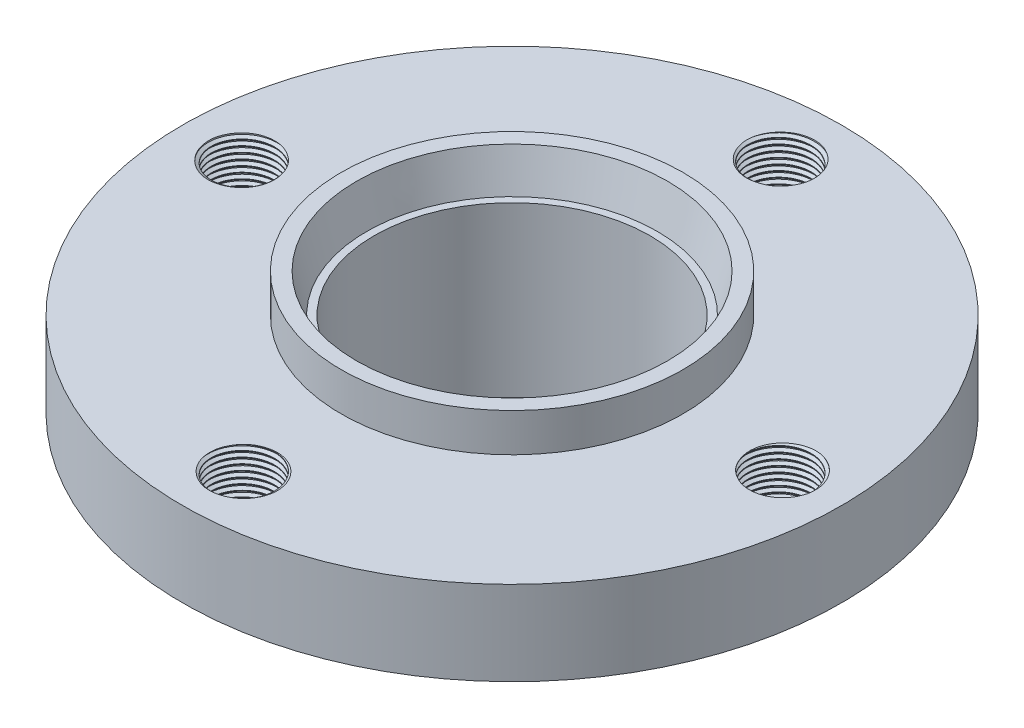
SolidWorks part; units mm, degrees
material "Chrome Stainless Steel"
ref_plane "Front Plane" through (0, 0, 0) normal (0, 0, 1) x (1, 0, 0)
ref_plane "Top Plane" through (0, 0, 0) normal (0, 1, 0) x (1, 0, 0)
ref_plane "Right Plane" through (0, 0, 0) normal (1, 0, 0) x (0, 0, -1)
sketch "Sketch1" plane through (0, 0, 0) normal (0, 0, 1) x (1, 0, 0)
  line L0 (539.3648, 0) -> (36, 0) construction
  line L1 (0, 0) -> (0, 26118.2396) construction
  line L2 (36, 0) -> (44.5, 0)
  line L3 (44.5, 0) -> (44.5, 22)
  line L4 (44.5, 22) -> (86, 22)
  line L5 (86, 22) -> (86, 44)
  line L6 (86, 44) -> (44.5984, 44)
  line L7 (44.5984, 44) -> (44.5984, 54)
  line L8 (44.5984, 54) -> (40.5984, 54)
  line L9 (40.5984, 54) -> (37.919, 44)
  line L10 (37.919, 44) -> (36, 44)
  line L11 (36, 44) -> (36, 0)
  line L12 (0, 0) -> (-26118.2396, 0) construction
  dimension "D1" = 8.5
  dimension "D2" = 22
  dimension "D3" = 41.5
  dimension "D4" = 10
  dimension "D5" = 54
  dimension "D6" = 4
  dimension "D7" = 10
  dimension "D8" = 105
  dimension "D9" = 36
  dimension "D10" = 41.4016
revolve "Revolve3" add sketch "Sketch1" angle 360 about L1
hole_wizard "Ø1.0mm Dowel Hole1" positions "Sketch3" profile "Sketch4" hole size "Ø1.0" standard "BSI" end condition through all
sketch "Sketch3" plane through (0, 44, 0) normal (0, 1, 0) x (1, 0, 0)
  point P0 (0, 70)
  dimension "D1" = 70
sketch "Sketch4" plane through (0, 44, -70) normal (1, 0, 0) x (0, 0, 1)
  line L0 (0, 0) -> (0, 44)
  line L1 (0, 44) -> (8.25, 44)
  line L2 (8.25, 44) -> (8.25, 0)
  line L5 (8.25, 0) -> (0, 0)
  line L11 (0, -6.35) -> (0, 107.95) construction
  dimension "Thru Hole Dia." = 16.5
  dimension "Thru Hole Depth" = 44
pattern_circular "CirPattern1" count 4 over 360 about axis through (0, 0, 0) along (0, 1, 0) of "Ø1.0mm Dowel Hole1"
thread "Thread1" pitch 1.5 start angle 0, offset 5, length 40, pitch 1.5, diameter 16.5
ref_plane "Plane1" through (-78.25, 49, 0) normal (0, 0, -1) x (1, 0, 0)
sketch "Thread Profile1" plane through (-78.25, 49, 0) normal (0, 0, -1) x (1, 0, 0)
  line L0 (0, 0) -> (0, 1.5) construction
  line L11 (0, 0) -> (0, 1.3125)
  line L12 (0, 1.3125) -> (-0.8119, 0.8437)
  line L13 (-0.8119, 0.8437) -> (-0.8119, 0.4687)
  line L15 (-0.8119, 0.4687) -> (0, 0)
  line L17 (-0.8119, 0.6562) -> (0, 0.6562) construction
  point P2 (0, 0)
  dimension "Pitch" = 1.5
  dimension "Profile_Angle" = 60
  dimension "Profile_Land" = 0.375
  dimension "Profile_Height" = 0.8119
pattern_circular "CirPattern2" count 4 over 360 about axis through (0, 44, 0) along (0, -1, 0) of "Thread1"
